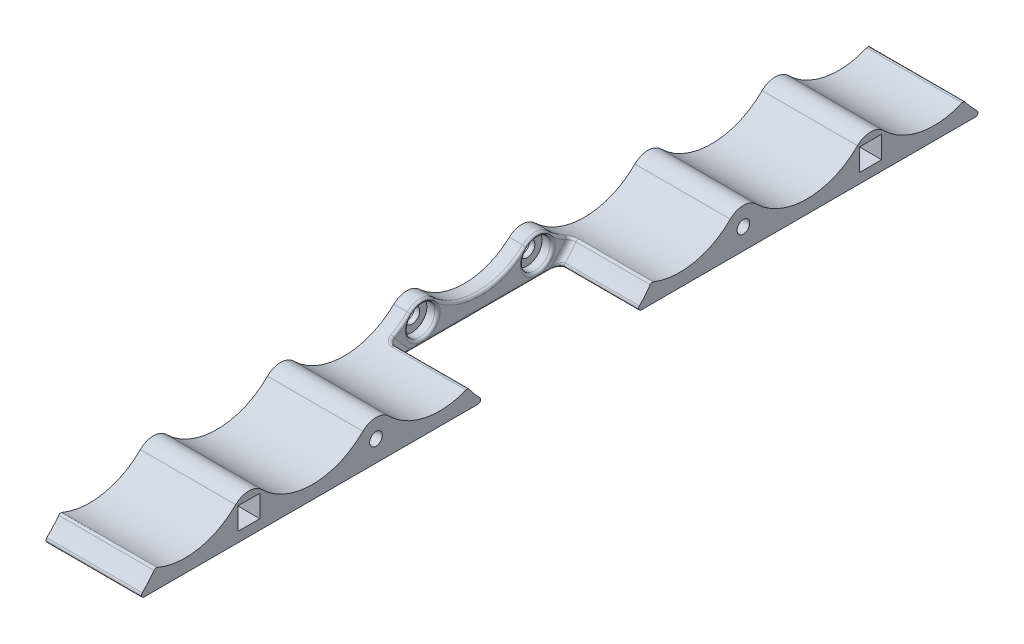
SolidWorks part; units mm, degrees
ref_plane "Front Plane" through (0, 0, 0) normal (0, 0, 1) x (1, 0, 0)
ref_plane "Top Plane" through (0, 0, 0) normal (0, 1, 0) x (1, 0, 0)
ref_plane "Right Plane" through (0, 0, 0) normal (1, 0, 0) x (0, 0, -1)
sketch "Sketch1" plane through (0, 0, 0) normal (1, 0, 0) x (0, 0, -1)
  line L0 (-126.5656, -24.6062) -> (126.5656, -24.6062)
  arc A0 (126.5656, -24.6062) -> (121.1052, -18.6881) centre (148.1579, 0.7938) cw
  arc A1 (-126.5656, -24.6062) -> (-121.1052, -18.6881) centre (-148.1579, 0.7937) ccw
  circle A2 centre (-93.1246, -18.3223) radius 5.5562 construction
  arc A3 (-93.1246, -9.0244) -> (-55.0246, -9.0244) centre (-74.0746, 0.7938) ccw construction
  circle A4 centre (-55.0246, -18.3223) radius 5.5562 construction
  arc A5 (-55.0246, -9.0244) -> (-17.2998, -9.7206) centre (-35.9746, 0.7938) ccw construction
  circle A6 centre (-17.2515, -18.6426) radius 5.5562 construction
  arc A7 (-17.2998, -9.7206) -> (17.2998, -9.7206) centre (0, 0) ccw construction
  circle A8 centre (17.2515, -18.6426) radius 5.5562 construction
  arc A9 (17.2998, -9.7206) -> (55.0246, -9.0244) centre (35.9746, 0.7937) ccw construction
  circle A10 centre (55.0246, -18.3223) radius 5.5562 construction
  circle A11 centre (93.1246, -18.3223) radius 5.5562 construction
  arc A12 (93.1246, -9.0244) -> (131.0767, -9.3061) centre (112.1746, 0.7937) ccw construction
  arc A13 (55.0246, -9.0244) -> (93.1246, -9.0244) centre (74.0746, 0.7937) ccw construction
  arc A14 (-89.2025, -14.3866) -> (-97.0466, -14.3866) centre (-93.1246, -18.3223) ccw
  arc A15 (-89.2025, -14.3866) -> (-58.9466, -14.3866) centre (-74.0746, 0.7938) ccw
  arc A16 (-51.1025, -14.3866) -> (-58.9466, -14.3866) centre (-55.0246, -18.3223) ccw
  arc A17 (-51.1025, -14.3866) -> (-21.1062, -14.641) centre (-35.9746, 0.7938) ccw
  arc A18 (-13.4777, -14.5645) -> (-21.1062, -14.641) centre (-17.2515, -18.6426) ccw
  arc A19 (-13.4777, -14.5645) -> (13.4777, -14.5645) centre (0, 0) ccw
  arc A20 (21.1062, -14.641) -> (13.4777, -14.5645) centre (17.2515, -18.6426) ccw
  arc A21 (21.1062, -14.641) -> (51.1025, -14.3866) centre (35.9746, 0.7937) ccw
  arc A22 (58.9466, -14.3866) -> (51.1025, -14.3866) centre (55.0246, -18.3223) ccw
  arc A23 (97.0466, -14.3866) -> (89.2025, -14.3866) centre (93.1246, -18.3223) ccw
  arc A24 (97.0466, -14.3866) -> (121.1052, -18.6881) centre (112.1746, 0.7937) ccw
  arc A25 (58.9466, -14.3866) -> (89.2025, -14.3866) centre (74.0746, 0.7937) ccw
  arc A26 (-131.0767, -9.3061) -> (-93.1246, -9.0244) centre (-112.1746, 0.7937) ccw construction
  arc A27 (-121.1052, -18.6881) -> (-97.0466, -14.3866) centre (-112.1746, 0.7937) ccw
  arc A28 (-138.4024, 32.6719) -> (-143.3009, 33.7755) centre (-148.1579, 0.7937) ccw construction
  point P3 (0, -24.6062)
  dimension "D1" = 24.6062
extrude "Boss-Extrude1" add sketch "Sketch1" along normal up to surface (28.575 mm away)
sketch "Sketch2" plane through (28.575, 0, 0) normal (1, 0, 0) x (0, 0, -1)
  circle A0 centre (0, 0) radius 33.3375
  dimension "D1" = 66.675
extrude "Cut-Extrude1" cut sketch "Sketch2" against normal blind 23.8125
sketch "Sketch3" plane through (28.575, 0, 0) normal (1, 0, 0) x (0, 0, -1)
  line L9 (-89.8226, -15.0203) -> (-96.4266, -15.0203)
  line L10 (-89.8226, -21.6243) -> (-89.8226, -15.0203)
  line L11 (-96.4266, -21.6243) -> (-89.8226, -21.6243)
  line L12 (-96.4266, -15.0203) -> (-96.4266, -21.6243)
  line L13 (-89.8226, -15.0203) -> (-96.4266, -15.0203)
  line L14 (-89.8226, -21.6243) -> (-89.8226, -15.0203)
  line L15 (-96.4266, -21.6243) -> (-89.8226, -21.6243)
  line L16 (-96.4266, -15.0203) -> (-96.4266, -21.6243)
  line L22 (89.8226, -21.6243) -> (96.4266, -21.6243)
  line L23 (96.4266, -21.6243) -> (96.4266, -15.0203)
  line L24 (96.4266, -15.0203) -> (89.8226, -15.0203)
  line L25 (89.8226, -15.0203) -> (89.8226, -21.6243)
  line L26 (89.8226, -21.6243) -> (96.4266, -21.6243)
  line L27 (96.4266, -21.6243) -> (96.4266, -15.0203)
  line L28 (96.4266, -15.0203) -> (89.8226, -15.0203)
  line L29 (89.8226, -15.0203) -> (89.8226, -21.6243)
  dimension "D1" = 0.127
  dimension "D2" = 0.127
extrude "Cut-Extrude2" cut sketch "Sketch3" against normal through all
sketch "Sketch4" plane through (28.575, 0, 0) normal (1, 0, 0) x (0, 0, -1)
  point P0 (-55.0246, -18.3223)
  point P3 (55.0246, -18.3223)
hole_wizard "#8 Clearance Hole1" positions "Sketch4" profile "Sketch5" hole size "#8" standard "ANSI Inch" end condition up to next
sketch "Sketch5" plane through (28.575, -18.3223, 55.0246) normal (0, 1, 0) x (0, 0, -1)
  line L0 (0, 0) -> (0, 28.575)
  line L1 (0, 28.575) -> (1.905, 28.575)
  line L2 (1.905, 28.575) -> (1.905, 0)
  line L5 (1.905, 0) -> (0, 0)
  line L11 (0, -6.35) -> (0, 107.95) construction
  dimension "Thru Hole Dia." = 3.81
  dimension "Thru Hole Depth" = 28.575
sketch "Sketch6" plane through (4.7625, 0, 0) normal (1, 0, 0) x (0, 0, -1)
  circle A0 centre (-17.2515, -18.6426) radius 4.445
  circle A1 centre (17.2515, -18.6426) radius 4.445
  dimension "D1" = 8.89
extrude "Cut-Extrude3" cut sketch "Sketch6" against normal blind 3.175
sketch "Sketch7" plane through (1.5875, 0, 0) normal (1, 0, 0) x (0, 0, -1)
  point P0 (-17.2515, -18.6426)
  point P3 (17.2515, -18.6426)
hole_wizard "#8 Clearance Hole2" positions "Sketch7" profile "Sketch8" hole size "#8" standard "ANSI Inch" end condition up to next
sketch "Sketch8" plane through (1.5875, -18.6426, 17.2515) normal (0, 1, 0) x (0, 0, -1)
  line L0 (0, 0) -> (0, 1.5875)
  line L1 (0, 1.5875) -> (2.286, 1.5875)
  line L2 (2.286, 1.5875) -> (2.286, 0)
  line L5 (2.286, 0) -> (0, 0)
  line L11 (0, -6.35) -> (0, 107.95) construction
  dimension "Thru Hole Dia." = 4.572
  dimension "Thru Hole Depth" = 1.5875
fillet "Fillet1" radius 1.5875 2 edges at (4.7625, -21.8856, -25.1478) (4.7625, -21.8856, 25.1478)
fillet "Fillet2" radius 0.7937 20 edges at (17.4625, -18.8803, -27.4758) (5.116, -18.6353, -26.9296) (4.7625, -16.5891, -23.4393) (4.7625, -13.0866, -17.3072) (17.4625, -18.8803, 27.4758) (5.3711, -18.7415, 27.1614) (4.7625, -16.5891, 23.4393) (4.7625, -13.0866, 17.3072) (17.4625, -24.6062, 22.4927) (5.2999, -24.6062, 21.9001) (17.4625, -24.6062, -22.4927) (5.5963, -24.6062, -22.2096) (4.7625, -18.6426, -21.6965) (4.7625, -18.6426, 12.8065) (4.7625, -19.8438, 0) (4.7625, -24.6062, 0) (14.2875, -24.6062, -126.5656) (14.2875, -18.6881, -121.1052) (14.2875, -24.6062, 126.5656) (14.2875, -18.6881, 121.1052)
